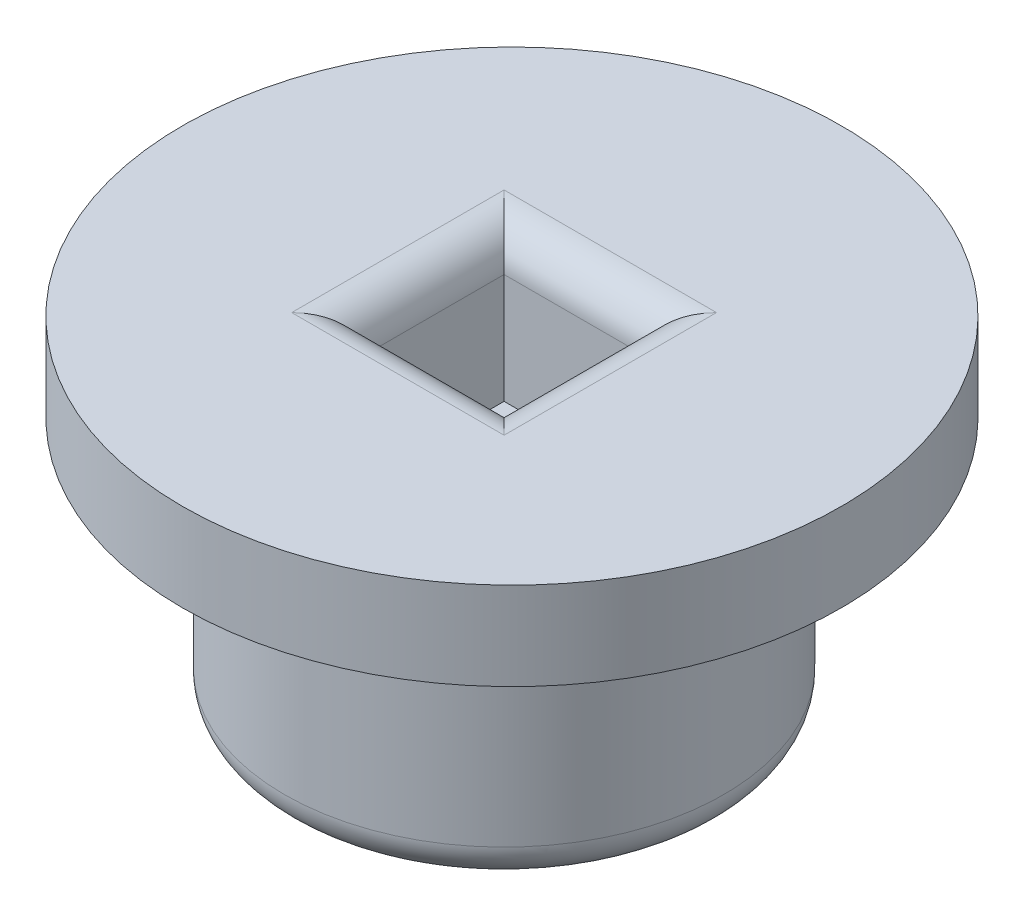
SolidWorks part; units mm, degrees
ref_plane "前视基准面" through (0, 0, 0) normal (0, 0, 1) x (1, 0, 0)
ref_plane "上视基准面" through (0, 0, 0) normal (0, 1, 0) x (1, 0, 0)
ref_plane "右视基准面" through (0, 0, 0) normal (1, 0, 0) x (0, 0, -1)
sketch "草图1" plane through (0, 0, 0) normal (0, 1, 0) x (1, 0, 0)
  circle A0 centre (0, 0) radius 3
  dimension "D1" = 6
extrude "凸台-拉伸1" add sketch "草图1" along normal blind 3.5 contours A0
sketch "草图2" plane through (0, 3.5, 0) normal (0, 1, 0) x (1, 0, 0)
  circle A0 centre (0.0949, 0.012) radius 4.5
  dimension "D1" = 9
extrude "凸台-拉伸2" add sketch "草图2" along normal blind 1.2
sketch "草图4" plane through (0, 4.7, 0) normal (0, 1, 0) x (1, 0, 0)
  line L1 (0.95, -0.95) -> (-0.95, -0.95)
  line L2 (0.95, -0.95) -> (0.95, 0.95)
  line L3 (0.95, 0.95) -> (-0.95, 0.95)
  line L4 (-0.95, -0.95) -> (-0.95, 0.95)
  line L5 (0.95, -0.95) -> (-0.95, 0.95) construction
  line L6 (0.95, 0.95) -> (-0.95, -0.95) construction
  circle A0 centre (0, 0) radius 3 construction
  point P0 (0, 0)
  dimension "D1" = 1.9
  dimension "D2" = 1.9
extrude "切除-拉伸1" cut sketch "草图4" against normal blind 2
fillet "圆角1" radius 0.5 1 edges at (0, 0, 3)
fillet "圆角2" radius 0.5 4 edges at (0, 4.7, 0.95) (-0.95, 4.7, 0) (0, 4.7, -0.95) (0.95, 4.7, 0)
